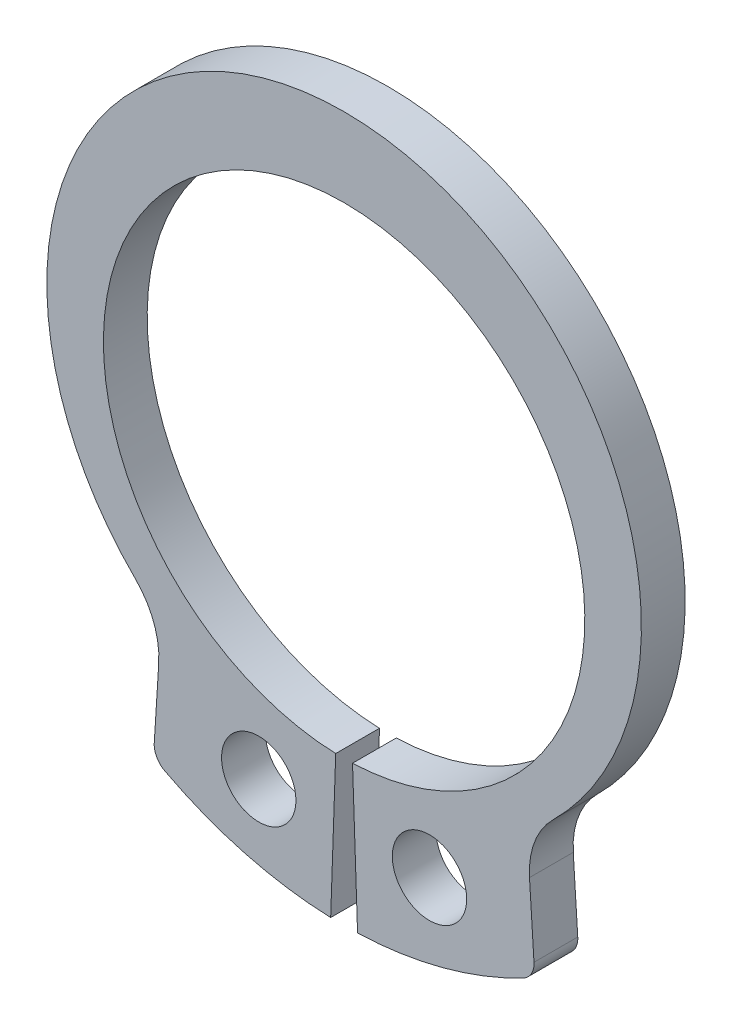
SolidWorks part; units mm, degrees
ref_plane "Front" through (0, 0, 0) normal (0, 0, 1) x (1, 0, 0)
ref_plane "Top" through (0, 0, 0) normal (0, 1, 0) x (1, 0, 0)
ref_plane "Right" through (0, 0, 0) normal (1, 0, 0) x (0, 0, -1)
sketch "Sketch1" plane through (0, 0, 0) normal (0, 0, 1) x (1, 0, 0)
  line L0 (0, 0) -> (-4.7631, -2.75) construction
  line L1 (0, 8.8) -> (0, -8.8) construction
  line L2 (-4.3566, -7.6521) -> (-4.1796, -4.8467) construction
  line L4 (-4.1796, -4.8467) -> (-4.7674, -5.5283) construction
  line L5 (-4.1796, -4.8467) -> (0, 0) construction
  line L6 (0, 5.5) -> (0, 7.3) construction
  line L7 (0, 7.3) -> (0, 6.4) construction
  line L8 (0, -5.5) -> (0, -8.8) construction
  line L9 (-2.4015, -8.4715) -> (0, 0) construction
  line L10 (0, 0) -> (-0.3073, -8.8) construction
  line L11 (-4.3566, -7.6521) -> (0, 0) construction
  line L12 (-4.2293, -5.6343) -> (-4.7724, -4.3258) construction
  line L13 (-4.5009, -4.98) -> (-4.1796, -4.8467) construction
  line L14 (-1.5001, -5.2915) -> (-2.4015, -8.4715) construction
  line L15 (-1.9508, -6.8815) -> (-1.133, -7.1133) construction
  arc A0 (0, 7.3) -> (-4.1796, -4.8467) centre (0, 0.5075) ccw construction
  circle A2 centre (0, 0) radius 7.3 construction
  arc A3 (-4.3566, -7.6521) -> (-0.3073, -8.8) centre (0, 0) ccw construction
  circle A4 centre (0, 0) radius 5.5 construction
  circle A6 centre (-1.9508, -6.8815) radius 0.85 construction
  arc A7 (-4.7724, -4.3258) -> (-4.2293, -5.6343) centre (-6.0556, -5.6254) cw construction
  circle A9 centre (0, 0) radius 6 construction
  circle A10 centre (0, 0) radius 5.75 construction
  point P5 (-4.7631, -2.75)
  point P24 (-3.6118, -6.3439)
  point P35 (0, 7.3)
  point P36 (0, 5.5)
  point P37 (0, -5.5)
  point P38 (0, -8.8)
  dimension "Hole Diameter" = 1.7
  dimension "D10" = 1.8263
  dimension "For OD" = 12
  dimension "ID" = 11
  dimension "Max Sec." = 1.8
  dimension "Lug Height" = 3.3
  dimension "D6" = 2
  dimension "D5" = 2.811
  dimension "D8" = 1.4167
  dimension "D3" = 120
  dimension "D2" = 4.25
  dimension "D4" = 1.4167
sketch "Sketch2" plane through (0, 0, 0) normal (-1, 0, 0) x (0, 1, 0)
  line L0 (-7.3, 0.5) -> (-7.3, -0.5) construction
  line L1 (7.3, -0.55) -> (7.3, 0.55) construction
  line L2 (0, 0.5) -> (0, -0.5) construction
  line L4 (-7.3, 0) -> (7.3, 0) construction
  point P3 (-7.3, 0)
  point P6 (0, 0)
  point P14 (7.3, 0)
  dimension "Thickness" = 1
  dimension "For Groove Width" = 1.1
sketch "Sketch4" plane through (0, 0, 0) normal (0, 0, 1) x (1, 0, 0)
  line L0 (-4.3566, -7.6521) -> (-4.1796, -4.8467) construction
  line L1 (-4.3566, -7.6521) -> (-4.1796, -4.8467)
  line L2 (0, 7.3) -> (0, 5.5)
  line L3 (-0.3073, -8.8) -> (-0.1919, -5.4966)
  line L4 (0, 0) -> (-0.3073, -8.8) construction
  arc A0 (0, 7.3) -> (-4.1796, -4.8467) centre (0, 0.5075) ccw construction
  arc A1 (-4.3566, -7.6521) -> (-0.3073, -8.8) centre (0, 0) ccw construction
  circle A2 centre (-1.9508, -6.8815) radius 0.85 construction
  arc A4 (0, 7.3) -> (-4.1796, -4.8467) centre (0, 0.5075) ccw
  arc A5 (-4.3566, -7.6521) -> (-0.3073, -8.8) centre (0, 0) ccw
  circle A6 centre (-1.9508, -6.8815) radius 0.85
  circle A7 centre (0, 0) radius 5.5 construction
  arc A8 (0, 5.5) -> (-0.1919, -5.4966) centre (0, 0) ccw
extrude "Boss-Extrude1" add sketch "Sketch4" along normal mid plane 1
fillet "Fillet1" radius 1.8263 1 edges at (-4.1796, -4.8467, 0)
fillet "Fillet2" radius 0.4566 1 edges at (-4.3566, -7.6521, 0)
mirror "Mirror1" about plane through (0, 7.3, 0.5) normal (-1, 0, 0) of bodies 109
sketch "Sketch3" plane through (0, 0, 0.5) normal (0, 0, 1) x (1, 0, 0)
  line L0 (4.1118, -3.6528) -> (4.7747, -4.3236) construction
  line L1 (4.7747, -4.3236) -> (5.4455, -3.6606) construction
  line L2 (0, 7.3) -> (0, 5.5) construction
  circle A0 centre (0, 0) radius 5.5 construction
  arc A1 (4.7747, -4.3236) -> (-4.7747, -4.3236) centre (0, 0.5075) ccw construction
equation "\"D1@Fillet1\" = \"D10@Sketch1\""
equation "\"D1@Fillet2\" = \"D10@Sketch1\" / 4"
equation "\"Thickness@Boss-Extrude1\"  = \"Ring Thickness@Sketch5\""
equation "\"D2@Sketch1\"=\"Hole Diameter@Sketch1\"*2.5"
equation "\"D4@Sketch1\"=\"D2@Sketch1\"/3"
equation "\"D8@Sketch1\"=\"D4@Sketch1\""
